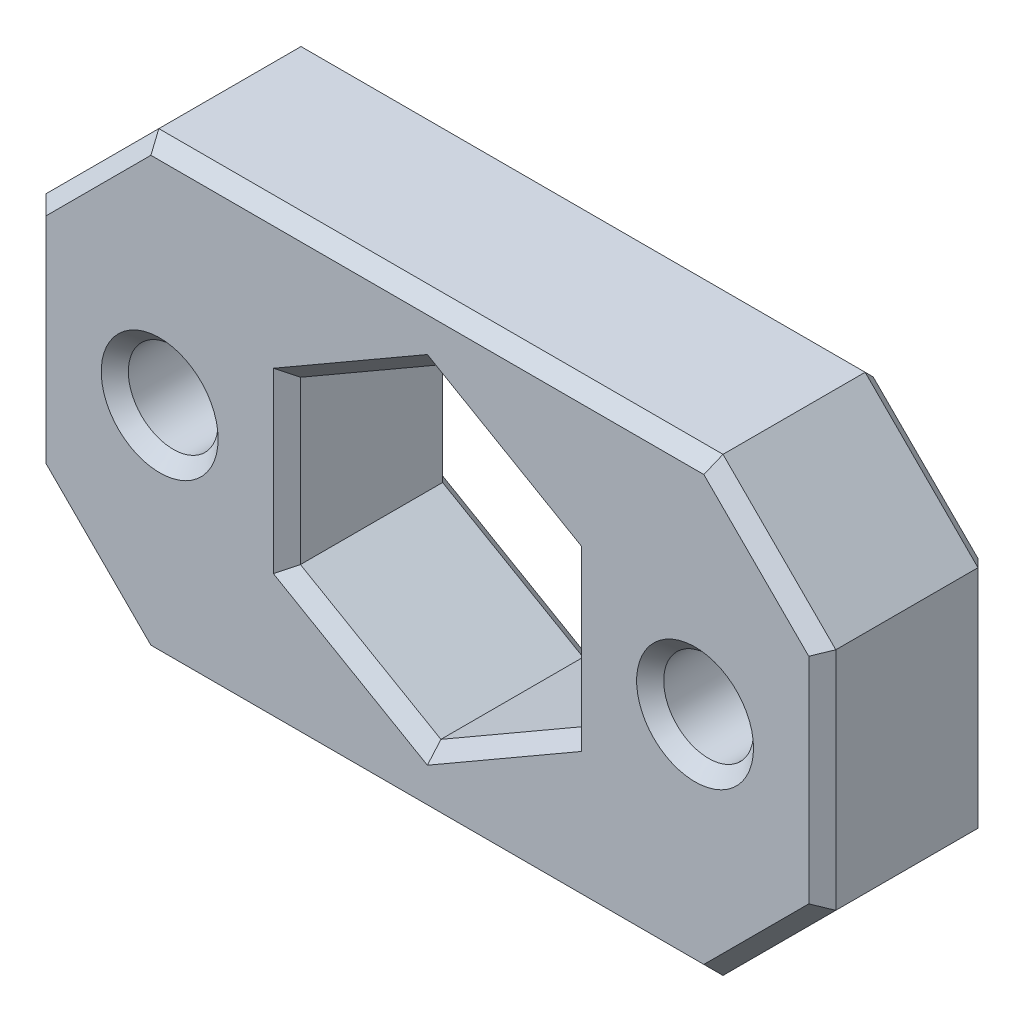
SolidWorks part; units mm, degrees
material "PET"
ref_plane "Front Plane" through (0, 0, 0) normal (0, 0, 1) x (1, 0, 0)
ref_plane "Top Plane" through (0, 0, 0) normal (0, 1, 0) x (1, 0, 0)
ref_plane "Right Plane" through (0, 0, 0) normal (1, 0, 0) x (0, 0, -1)
sketch "Sketch1" plane through (0, 0, 0) normal (0, 0, 1) x (1, 0, 0)
  line L0 (-37.0142, -65.193) -> (-37.0142, -354.753) construction
  line L1 (43.1742, -197.9364) -> (43.1742, -188.8076)
  line L2 (43.1742, -188.8076) -> (35.2684, -184.2432)
  line L3 (35.2684, -184.2432) -> (27.3627, -188.8076)
  line L4 (27.3627, -188.8076) -> (27.3627, -197.9364)
  line L5 (27.3627, -197.9364) -> (35.2684, -202.5008)
  line L6 (35.2684, -202.5008) -> (43.1742, -197.9364)
  line L7 (28.1247, -189.2475) -> (28.1247, -197.4964) construction
  line L9 (57.4934, -206.072) -> (13.0434, -206.072)
  line L10 (57.4934, -206.072) -> (57.4934, -180.672)
  line L11 (57.4934, -180.672) -> (13.0434, -180.672)
  line L12 (13.0434, -206.072) -> (13.0434, -180.672)
  line L13 (57.4934, -206.072) -> (13.0434, -180.672) construction
  line L14 (57.4934, -180.672) -> (13.0434, -206.072) construction
  circle A0 centre (35.2684, -193.372) radius 7.9057 construction
  dimension "D1" = 0.762
  dimension "D2" = 25.4
  dimension "D3" = 44.45
extrude "Boss-Extrude1" add sketch "Sketch1" along normal blind 9.525
chamfer "Chamfer1" distance 6.35 angle 45 4 edges at (57.4934, -180.672, 4.7625) (57.4934, -206.072, 4.7625) (13.0434, -206.072, 4.7625) (13.0434, -180.672, 4.7625)
hole_wizard "Hole1" positions "Sketch2" profile "Sketch3" legacy
sketch "Sketch2" plane through (0, 0, 0) normal (0, 0, -1) x (-1, 0, 0)
  line L0 (-43.1742, -193.372) -> (-57.4934, -193.372) construction
  line L1 (-43.1742, -197.9364) -> (-43.1742, -188.8076) construction
  line L2 (-57.4934, -199.722) -> (-57.4934, -187.022) construction
  line L4 (-27.3627, -193.372) -> (-13.0434, -193.372) construction
  line L5 (-27.3627, -188.8076) -> (-27.3627, -197.9364) construction
  line L6 (-13.0434, -187.022) -> (-13.0434, -199.722) construction
  point P16 (-50.3338, -193.372)
  point P18 (-20.203, -193.372)
sketch "Sketch3" plane through (20.203, -193.372, 0) normal (1, 0, 0) x (0, 1, 0)
  line L0 (0, 0) -> (0, 4.699)
  line L1 (0, 4.699) -> (2.8702, 4.699)
  line L2 (2.8702, 4.699) -> (2.9972, 0)
  line L3 (2.9972, 0) -> (0, 0)
  line L4 (0, 110) -> (0, -10) construction
  dimension "Minor Diameter" = 5.7404
  dimension "Depth" = 4.699
  dimension "Major Diameter" = 5.9944
hole_wizard "#8 (0.199) Diameter Hole1" positions "Sketch4" profile "Sketch5" hole size "#8" standard "ANSI Inch" end condition through all
sketch "Sketch4" plane through (0, 0, 0) normal (0, 0, -1) x (-1, 0, 0)
  point P0 (-50.3338, -193.372)
  point P3 (-20.203, -193.372)
sketch "Sketch5" plane through (50.3338, -193.372, 0) normal (1, 0, 0) x (0, 1, 0)
  line L0 (0, 0) -> (0, 9.525)
  line L1 (0, 9.525) -> (2.5273, 9.525)
  line L2 (2.5273, 9.525) -> (2.5273, 0)
  line L5 (2.5273, 0) -> (0, 0)
  line L11 (0, -6.35) -> (0, 107.95) construction
  dimension "Thru Hole Dia." = 5.0546
  dimension "Thru Hole Depth" = 9.525
chamfer "Chamfer2" distance 0.762 angle 45 30 edges at (54.3184, -202.897, 0) (57.4934, -193.372, 0) (35.2684, -180.672, 0) (54.3184, -183.847, 0) (47.8065, -193.372, 9.525) (39.2213, -186.5254, 9.525) (31.3155, -186.5254, 9.525) (27.3627, -193.372, 9.525) (31.3155, -200.2186, 9.525) (39.2213, -200.2186, 9.525) (43.1742, -193.372, 9.525) (54.3184, -202.897, 9.525) (35.2684, -206.072, 9.525) (16.2184, -202.897, 9.525) (13.0434, -193.372, 9.525) (16.2184, -183.847, 9.525) (35.2684, -180.672, 9.525) (54.3184, -183.847, 9.525) (57.4934, -193.372, 9.525) (17.6757, -193.372, 9.525) (39.2213, -200.2186, 0) (31.3155, -200.2186, 0) (27.3627, -193.372, 0) (31.3155, -186.5254, 0) (39.2213, -186.5254, 0) (43.1742, -193.372, 0) (35.2684, -206.072, 0) (16.2184, -202.897, 0) (13.0434, -193.372, 0) (16.2184, -183.847, 0)
